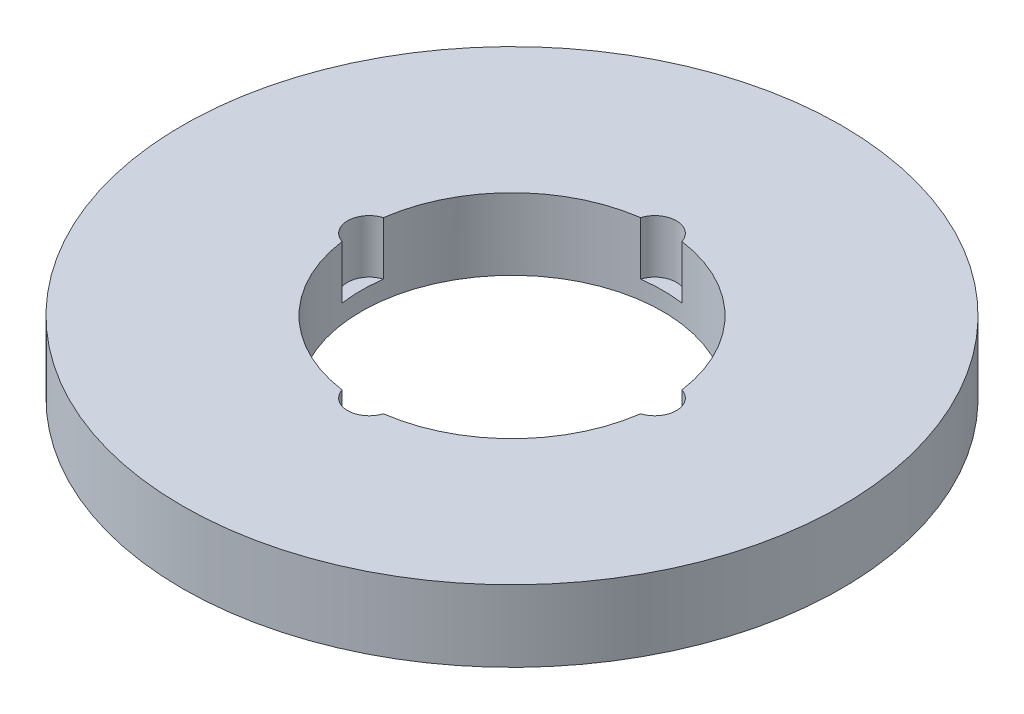
SolidWorks part; units mm, degrees
ref_plane "Front Plane" through (0, 0, 0) normal (0, 0, 1) x (1, 0, 0)
ref_plane "Top Plane" through (0, 0, 0) normal (0, 1, 0) x (1, 0, 0)
ref_plane "Right Plane" through (0, 0, 0) normal (1, 0, 0) x (0, 0, -1)
sketch "Sketch1" plane through (0, 0, 0) normal (0, 1, 0) x (1, 0, 0)
  circle A0 centre (0, 0) radius 87.5
  dimension "FLANGE_OD" = 175
extrude "Boss-Extrude1" add sketch "Sketch1" along normal blind 19
sketch "Sketch2" plane through (0, 0, 0) normal (0, 1, 0) x (1, 0, 0)
  circle A0 centre (0, 0) radius 40
  dimension "BORE_D" = 80
extrude "Cut-Extrude1" cut sketch "Sketch2" along normal through all
sketch "Sketch3" plane through (0, 19, 0) normal (0, 1, 0) x (1, 0, 0)
  circle A0 centre (0, 0) radius 37.8954 construction
  circle A1 centre (-37.8954, 0) radius 5.7554
  dimension "BOLT_D" = 11.5108
  dimension "BOLT_PCD" = 75.7909
extrude "Cut-Extrude2" cut sketch "Sketch3" against normal blind 14.1505
pattern_circular "CirPattern1" count 4 over 360 about axis through (0, 0, 0) along (0, 1, 0) of "Cut-Extrude2"
